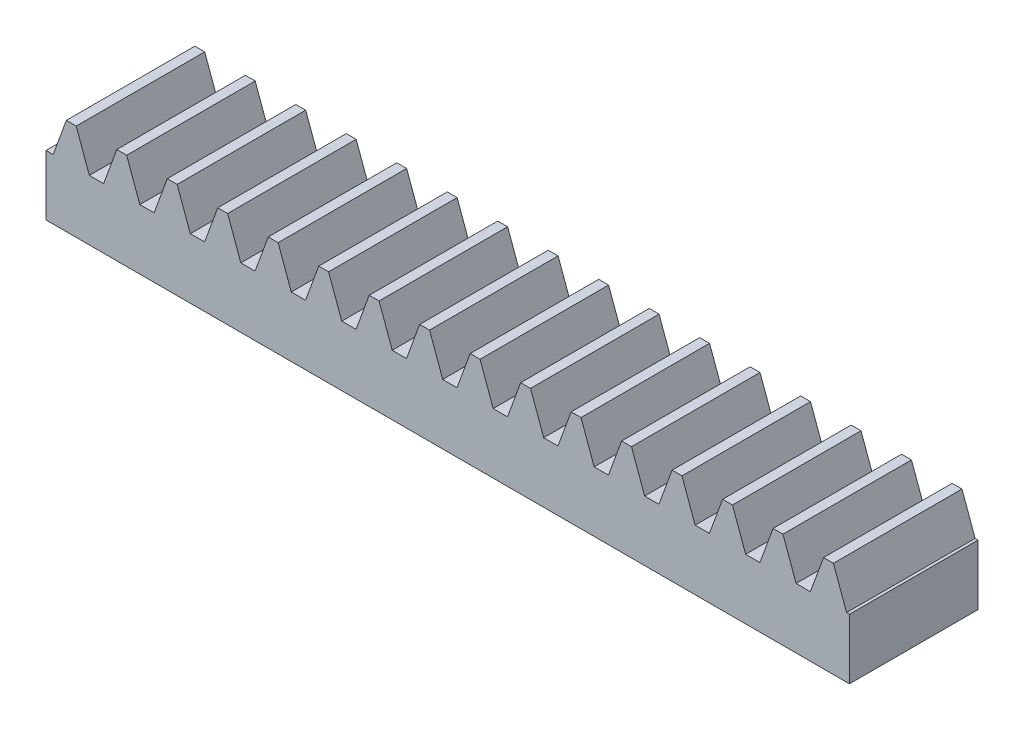
SolidWorks part; units mm, degrees
ref_plane "Plane1" through (0, 0, 0) normal (0, 0, 1) x (1, 0, 0)
ref_plane "Plane2" through (0, 0, 0) normal (0, 1, 0) x (1, 0, 0)
ref_plane "Plane3" through (0, 0, 0) normal (1, 0, 0) x (0, 0, -1)
sketch "HoldingSke" plane through (0, 0, 0) normal (0, 1, 0) x (1, 0, 0)
  line L0 (0, 0) -> (0.1392, 0.9903)
  line L1 (-15, 0) -> (100, 0) construction
  line L2 (0, 0) -> (-2.1039, 2.3779)
  line L3 (0, 0) -> (-11.863, 4.5341)
  line L4 (0, 0) -> (8.2587, 2.5249)
  line L5 (0, 0) -> (-23.7986, -8.8762)
  line L6 (0, 0) -> (-10.5278, -7.1032)
  line L9 (-71.009, 38.7566) -> (-24.0243, 55.8576)
  line L10 (-76.2, 3.3779) -> (-71.2, 3.3779)
  line L11 (0, 0) -> (-7, 0)
  line L12 (-76.2, 101.6) -> (-76.162, 101.6)
  line L13 (24.9733, 27.94) -> (52.9518, 28.4284)
  line L14 (24.9733, 27.94) -> (24.9743, 27.94)
  line L15 (24.9733, 27.94) -> (100.4006, 29.5858)
  circle A0 centre (0, 0) radius 19.05
  circle A1 centre (0, 0) radius 2.5
  circle A2 centre (0, 0) radius 12.7
  dimension "MPH" = 5
  dimension "Diameter" = 38.1
  dimension "Num_teeth" = 17
  dimension "Pitch" = 1
  dimension "Width" = 7
  dimension "Show_teeth" = 998
  dimension "Thickness" = 12.7
  dimension "Ap" = 20
  dimension "Pitch_height" = 5
  dimension "Backlash" = 0.038
  dimension "Addendum_fac" = 1
  dimension "Dedendum_fac" = 1.25
  dimension "Clearance_fac" = 0.25
  dimension "Dedendum_add" = 0.001
  dimension "Length" = 50
  dimension "Module" = 1
sketch "BlankSke" plane through (0, 0, 0) normal (0, 0, 1) x (1, 0, 0)
  line L1 (0, 0) -> (50, 0)
  line L2 (0, 0) -> (0, 6)
  line L3 (0, 6) -> (50, 6)
  line L4 (50, 0) -> (50, 6)
  dimension "Length" = 50
  dimension "Blank_height" = 6
extrude "Blank" add sketch "BlankSke" against normal blind 8
sketch "TooCutSkeIll" plane through (0, 0, 0) normal (0, 0, 1) x (1, 0, 0)
  line L0 (-1.2538, 5.9737) -> (-0.5045, 3.9152)
  line L1 (-0.2687, 3.75) -> (0.2687, 3.75)
  line L2 (0.5045, 3.9152) -> (1.2538, 5.9737)
  line L3 (50, 6) -> (0, 6) construction
  line L4 (0, 0) -> (0, 64.897) construction
  line L5 (-13.208, 5) -> (12.954, 5) construction
  line L6 (0, 0) -> (50, 0) construction
  line L7 (0.8994, 5) -> (0.8994, 48.7463) construction
  line L8 (-0.8994, 5) -> (-0.8994, 48.7463) construction
  line L9 (1.2914, 6) -> (1.2914, 6.0254)
  line L10 (-1.2914, 6) -> (-1.2914, 6.0254)
  line L11 (-1.2914, 6.0254) -> (1.2914, 6.0254)
  arc A0 (0.2687, 3.75) -> (0.5045, 3.9152) centre (0.2687, 4.001) ccw
  arc A1 (-0.5045, 3.9152) -> (-0.2687, 3.75) centre (-0.2687, 4.001) ccw
  arc A2 (1.2914, 6) -> (1.2538, 5.9737) centre (1.2914, 5.96) ccw
  arc A3 (-1.2538, 5.9737) -> (-1.2914, 6) centre (-1.2914, 5.96) ccw
  dimension "Root_fillet" = 0.251
  dimension "Break_rad" = 0.04
  dimension "Pitch_height" = 5
  dimension "Gap_width" = 1.7988
  dimension "Dedendum" = 1.25
  dimension "Addendum_plus" = 1.0254
  dimension "Pressure_angle" = 20
extrude "ToothCutIll" [suppressed] cut sketch "TooCutSkeIll" against normal through all
sketch "TooCutSkeSim" plane through (0, 0, 0) normal (0, 0, 1) x (1, 0, 0)
  line L0 (0.4444, 3.75) -> (-0.4444, 3.75)
  line L1 (1.2726, 6.0254) -> (0.4444, 3.75)
  line L2 (0, 17.4625) -> (0, 53.467) construction
  line L3 (1.2726, 6.0254) -> (-1.2726, 6.0254)
  line L6 (-1.2726, 6.0254) -> (-0.4444, 3.75)
  line L9 (-0.8994, 5) -> (0.8994, 5) construction
  line L10 (0, 0) -> (50, 0) construction
  line L11 (0.8994, 5) -> (0.8994, 53.467) construction
  line L12 (-0.8994, 5) -> (-0.8994, 53.467) construction
  dimension "Pitch_height" = 5
  dimension "Pressure_angle" = 20
  dimension "Gap_width" = 1.7988
  dimension "Dedendum" = 1.25
  dimension "Addendum_plus" = 1.0254
extrude "ToothCutSim" cut sketch "TooCutSkeSim" against normal through all
pattern_linear "TeethCuts" count 17 spacing 3.1416 along (1, 0, 0) of "ToothCutIll", "ToothCutSim"
equation "' \"Module@HoldingSke\" = 6.35"
equation "' \"Num_teeth@HoldingSke\" = 12"
equation "' \"Ap@HoldingSke\" =  20"
equation "' \"Width@HoldingSke\" = 0.25 * 25.4"
equation "' \"Show_teeth@HoldingSke\" = 500"
equation "' \"Backlash@HoldingSke\" = 0.009 * 25.4"
equation "' \"Addendum_fac@HoldingSke\" = 1.0"
equation "' \"Dedendum_fac@HoldingSke\" = 1.25"
equation "' \"Dedendum_add@HoldingSke\" = 0.00005 * 25.4"
equation "' \"Clearance_fac@HoldingSke\" = 0.25"
equation "' \"Pitch_height@HoldingSke\" = 1 * 25.4"
equation "' \"Length@HoldingSke\" = 4.71 * 25.4"
equation "\"Pitch@HoldingSke\" = 1 / \"Module@HoldingSke\""
equation "\"MPH@HoldingSke\" = \"Dedendum_fac@HoldingSke\" / \"Pitch@HoldingSke\" + 2 * \"Dedendum_add@HoldingSke\" + 0.002 * 25.4"
equation "\"MPH@HoldingSke\" = ((sgn( \"MPH@HoldingSke\" - \"Pitch_height@HoldingSke\")+1)*( \"MPH@HoldingSke\" - \"Pitch_height@HoldingSke\"))/2 + \"Pitch_height@HoldingSke\""
equation "\"Blank_height@BlankSke\"=6"
equation "\"Length@BlankSke\" =  \"Length@HoldingSke\""
equation "\"Face_width@Blank\"=8"
equation "\"Pressure_angle@TooCutSkeIll\" = \"Ap@HoldingSke\""
equation "\"Addendum_plus@TooCutSkeIll\" =  \"Addendum_fac@HoldingSke\"  / \"Pitch@HoldingSke\" + 0.001 *25.4"
equation "\"Dedendum@TooCutSkeIll\" = \"Dedendum_fac@HoldingSke\"  / \"Pitch@HoldingSke\""
equation "\"Pitch_height@TooCutSkeIll\" =  \"MPH@HoldingSke\""
equation "\"Gap_width@TooCutSkeIll\" = 3.14159265 / 2 / \"Pitch@HoldingSke\" + 6 * \"Backlash@HoldingSke\""
equation "\"Pressure_angle@TooCutSkeSim\" = \"Ap@HoldingSke\""
equation "\"Addendum_plus@TooCutSkeSim\" =  \"Addendum_fac@HoldingSke\"  / \"Pitch@HoldingSke\" + 0.001 * 25.4"
equation "\"Dedendum@TooCutSkeSim\" = \"Dedendum_fac@HoldingSke\"  / \"Pitch@HoldingSke\""
equation "\"Pitch_height@TooCutSkeSim\" =  \"MPH@HoldingSke\""
equation "\"Gap_width@TooCutSkeSim\" = 3.14159265 / 2 / \"Pitch@HoldingSke\" + 6 * \"Backlash@HoldingSke\""
equation "\"Root_fillet@TooCutSkeIll\" = \"Clearance_fac@HoldingSke\" / \"Pitch@HoldingSke\" + \"Dedendum_add@HoldingSke\""
equation "\"Break_rad@TooCutSkeIll\" = 0.02 / \"Pitch@HoldingSke\" * 2"
equation "\"Linear_pitch@TeethCuts\" = 3.14159265 / \"Pitch@HoldingSke\""
equation "\"Num_teeth@HoldingSke\" = int( ( \"Length@HoldingSke\" + 0 ) / (3.14159265 / \"Pitch@HoldingSke\")) + 0.9999  + 1"
equation " \"Num_teeth@TeethCuts\" = int( \"Show_teeth@HoldingSke\" ) + 1"
equation " \"Num_teeth@TeethCuts\" = ((sgn( \"Num_teeth@TeethCuts\" - \"Num_teeth@HoldingSke\" )-1)*( \"Num_teeth@TeethCuts\" - \"Num_teeth@HoldingSke\" ))/-2+ \"Num_teeth@HoldingSke\""
equation " \"Num_teeth@TeethCuts\" = ((sgn( \"Num_teeth@TeethCuts\" - 2.0)+1)*( \"Num_teeth@TeethCuts\" - 2.0))/2 +2.0"
